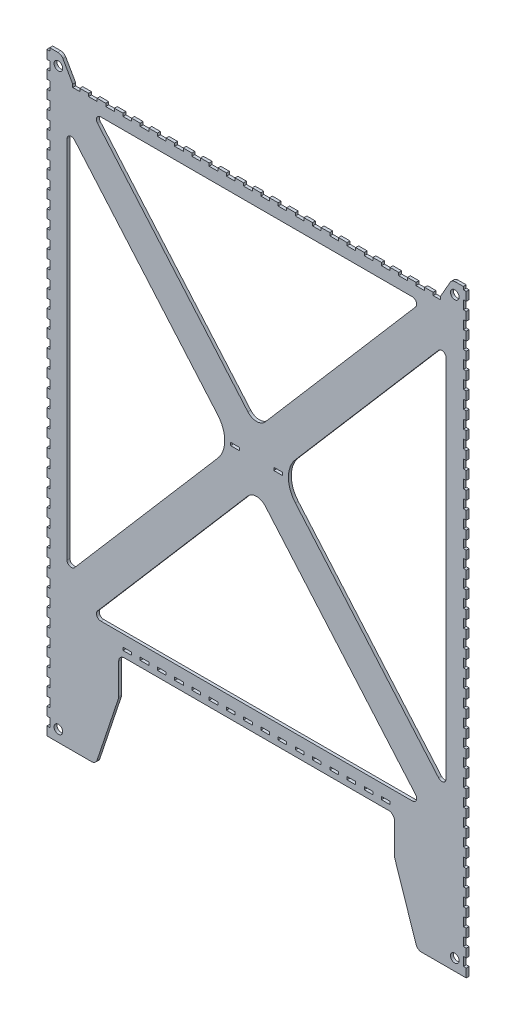
SolidWorks part; units mm, degrees
material "ABS"
ref_plane "Front Plane" through (0, 0, 0) normal (0, 0, 1) x (1, 0, 0)
ref_plane "Top Plane" through (0, 0, 0) normal (0, 1, 0) x (1, 0, 0)
ref_plane "Right Plane" through (0, 0, 0) normal (1, 0, 0) x (0, 0, -1)
sketch "Sketch1" plane through (0, 0, 0) normal (0, 0, 1) x (1, 0, 0)
  line L1 (-114.3, -127) -> (114.3, -127)
  line L2 (-114.3, -127) -> (-114.3, 127)
  line L3 (-114.3, 127) -> (114.3, 127)
  line L4 (114.3, -127) -> (114.3, 127)
  line L5 (-114.3, -127) -> (114.3, 127) construction
  line L6 (-114.3, 127) -> (114.3, -127) construction
  point P0 (0, 0)
  dimension "D1" = 254
  dimension "D2" = 228.6
extrude "Boss-Extrude1" add sketch "Sketch1" along normal mid plane 1.5875
sketch "Sketch2" plane through (0, 0, 0.7937) normal (0, 0, 1) x (1, 0, 0)
  line L0 (-114.3, -127) -> (-114.3, -190.5)
  line L1 (-114.3, -190.5) -> (-88.9, -190.5)
  line L2 (-88.9, -190.5) -> (-76.2, -152.4)
  line L3 (-76.2, -152.4) -> (-76.2, -127)
  line L4 (-114.3, -127) -> (114.3, -127) construction
  line L5 (-76.2, -127) -> (-114.3, -127)
  line L6 (114.3, -127) -> (114.3, -190.5)
  line L7 (114.3, -190.5) -> (88.9, -190.5)
  line L8 (88.9, -190.5) -> (76.2, -152.4)
  line L9 (76.2, -152.4) -> (76.2, -127)
  line L10 (114.3, -127) -> (76.2, -127)
  line L11 (-114.3, 127) -> (-114.3, 139.7)
  line L12 (-114.3, 139.7) -> (-107.95, 139.7)
  line L13 (-107.95, 139.7) -> (-101.6, 128.5875)
  line L14 (114.3, 127) -> (-114.3, 127) construction
  line L15 (-101.6, 127) -> (-114.3, 127)
  line L16 (114.3, 127) -> (114.3, 139.7)
  line L17 (114.3, 139.7) -> (107.95, 139.7)
  line L18 (-101.6, 128.5875) -> (-101.6, 127)
  line L19 (101.6, 127) -> (114.3, 127)
  line L20 (107.95, 139.7) -> (101.6, 128.5875)
  line L21 (101.6, 128.5875) -> (101.6, 127)
  dimension "D1" = 63.5
  dimension "D2" = 25.4
  dimension "D3" = 25.4
  dimension "D4" = 38.1
  dimension "D5" = 12.7
  dimension "D6" = 6.35
  dimension "D7" = 12.7
  dimension "D8" = 1.5875
extrude "Boss-Extrude2" add sketch "Sketch2" against normal up to surface (1.5875 mm away) up to face at (0, 0, -0.7937)
sketch "Sketch4" plane through (0, 0, 0.7937) normal (0, 0, 1) x (1, 0, 0)
  line L0 (-114.3, 139.7) -> (-114.3, -190.5) construction
  line L1 (-114.3, 138.1125) -> (-115.8875, 138.1125)
  line L2 (-114.3, 138.1125) -> (-114.3, 133.35)
  line L3 (-114.3, 133.35) -> (-115.8875, 133.35)
  line L4 (-115.8875, 138.1125) -> (-115.8875, 133.35)
  line L5 (-107.95, 139.7) -> (-114.3, 139.7) construction
  dimension "D1" = 4.7625
  dimension "D2" = 1.5875
  dimension "D3" = 1.5875
extrude "Boss-Extrude3" add sketch "Sketch4" against normal up to surface (1.5875 mm away) up to face at (1.5875, -16.5199, -0.7937)
pattern_linear "LPattern1" count 35 spacing 9.525 along (0, -1, 0) of "Boss-Extrude3"
mirror "Mirror1" about plane through (0, 0, 0) normal (1, 0, 0) of "LPattern1"
sketch "Sketch5" plane through (0, 0, 0.7937) normal (0, 0, 1) x (1, 0, 0)
  line L0 (101.6, 127) -> (-101.6, 127) construction
  line L1 (-97.6312, 127) -> (-92.8688, 127)
  line L2 (-97.6312, 127) -> (-97.6313, 128.5875)
  line L3 (-97.6313, 128.5875) -> (-92.8688, 128.5875)
  line L4 (-92.8688, 127) -> (-92.8688, 128.5875)
  line L6 (-101.6, 127) -> (-101.6, 128.5875) construction
  dimension "D1" = 4.7625
  dimension "D2" = 1.5875
  dimension "D3" = 3.9688
extrude "Boss-Extrude4" add sketch "Sketch5" against normal up to surface (1.5875 mm away) up to face at (0.087, -23.4129, -0.7937)
pattern_linear "LPattern2" count 21 spacing 9.525 along (1, 0, 0) of "Boss-Extrude4"
mirror "Mirror2" about plane through (0, 0, 0) normal (0, 1, 0) of "LPattern2"
sketch "Sketch3" plane through (0, 0, 0.7937) normal (0, 0, 1) x (1, 0, 0)
  line L0 (-91.3046, 120.65) -> (91.3046, 120.65)
  line L1 (91.3046, 120.65) -> (0, 14.561)
  line L2 (0, 14.561) -> (-91.3046, 120.65)
  line L3 (-104.775, 107.1796) -> (-104.775, -107.1796)
  line L4 (-104.775, -107.1796) -> (-12.5318, 0)
  line L5 (-12.5318, 0) -> (-104.775, 107.1796)
  line L6 (104.775, 107.1796) -> (12.5318, 0)
  line L7 (12.5318, 0) -> (104.775, -107.1796)
  line L8 (104.775, -107.1796) -> (104.775, 107.1796)
  line L9 (91.3046, -120.65) -> (-91.3046, -120.65)
  line L10 (-91.3046, -120.65) -> (0, -14.561)
  line L11 (0, -14.561) -> (91.3046, -120.65)
  line L12 (-104.775, 107.1796) -> (-91.3046, 107.1796) construction
  line L13 (104.775, -120.65) -> (-104.775, -120.65) construction
  line L14 (104.775, -120.65) -> (104.775, 120.65) construction
  line L15 (104.775, 120.65) -> (-104.775, 120.65) construction
  line L16 (-104.775, -120.65) -> (-104.775, 120.65) construction
  line L17 (104.775, -120.65) -> (-104.775, 120.65) construction
  line L18 (104.775, 120.65) -> (-104.775, -120.65) construction
  line L19 (-91.3046, 107.1796) -> (-91.3046, 120.65) construction
  line L20 (91.3046, 120.65) -> (91.3046, 107.1796) construction
  line L21 (91.3046, 107.1796) -> (104.775, 107.1796) construction
  line L22 (-104.775, 107.1796) -> (-91.3046, 120.65) construction
  line L23 (91.3046, 120.65) -> (104.775, 107.1796) construction
  line L24 (-104.775, -107.1796) -> (-91.3046, -107.1796) construction
  line L25 (-91.3046, -107.1796) -> (-91.3046, -120.65) construction
  line L26 (91.3046, -120.65) -> (91.3046, -107.1796) construction
  line L27 (91.3046, -107.1796) -> (104.775, -107.1796) construction
  point P9 (0, 0)
  dimension "D1" = 209.55
  dimension "D2" = 241.3
  dimension "D3" = 19.05
extrude "Cut-Extrude1" cut sketch "Sketch3" against normal through all
fillet "Fillet1" radius 15.875 2 edges at (12.5318, 0, 0) (-12.5318, 0, 0)
fillet "Fillet2" radius 2.3813 8 edges at (104.775, -107.1796, 0) (91.3046, -120.65, 0) (91.3046, 120.65, 0) (104.775, 107.1796, 0) (-91.3046, 120.65, 0) (-104.775, 107.1796, 0) (-104.775, -107.1796, 0) (-91.3046, -120.65, 0)
fillet "Fillet3" radius 6.35 2 edges at (0, -14.561, 0) (0, 14.561, 0)
sketch "Sketch6" plane through (0, 0, 0.7937) normal (0, 0, 1) x (1, 0, 0)
  line L0 (-9.525, 0.7938) -> (9.525, -0.7937) construction
  line L1 (-14.2875, -0.7937) -> (-9.525, -0.7937)
  line L2 (-14.2875, -0.7937) -> (-14.2875, 0.7938)
  line L3 (-14.2875, 0.7938) -> (-9.525, 0.7938)
  line L4 (-9.525, -0.7937) -> (-9.525, 0.7938)
  line L5 (-14.2875, -0.7937) -> (-9.525, 0.7938) construction
  line L6 (-14.2875, 0.7938) -> (-9.525, -0.7937) construction
  line L7 (9.525, -0.7937) -> (14.2875, -0.7937)
  line L8 (9.525, -0.7937) -> (9.525, 0.7938)
  line L9 (9.525, 0.7938) -> (14.2875, 0.7938)
  line L10 (14.2875, -0.7937) -> (14.2875, 0.7938)
  line L11 (9.525, -0.7937) -> (14.2875, 0.7938) construction
  line L12 (9.525, 0.7938) -> (14.2875, -0.7937) construction
  point P0 (-11.9062, 0)
  point P5 (11.9063, 0)
  dimension "D1" = 4.7625
  dimension "D2" = 19.05
  dimension "D3" = 1.5875
extrude "Cut-Extrude2" cut sketch "Sketch6" against normal through all
sketch "Sketch7" plane through (0, 0, -0.7937) normal (0, 0, -1) x (-1, 0, 0)
  line L0 (-76.2, -128.5875) -> (-73.8188, -128.5875) construction
  line L1 (-76.2, -128.5875) -> (76.2, -128.5875)
  line L2 (-76.2, -128.5875) -> (-76.2, -131.7625)
  line L3 (-76.2, -131.7625) -> (76.2, -131.7625)
  line L4 (76.2, -128.5875) -> (76.2, -131.7625)
  line L5 (76.2, -152.4) -> (76.2, -128.5875) construction
  dimension "D1" = 3.175
extrude "Boss-Extrude5" add sketch "Sketch7" against normal up to surface (1.5875 mm away) up to face at (11.9062, 0, 0.7937)
sketch "Sketch8" plane through (0, 0, 0.7937) normal (0, 0, 1) x (1, 0, 0)
  line L1 (-109.5375, -184.15) -> (109.5375, -184.15) construction
  line L2 (-109.5375, -184.15) -> (-109.5375, 133.35) construction
  line L3 (-109.5375, 133.35) -> (109.5375, 133.35) construction
  line L4 (109.5375, -184.15) -> (109.5375, 133.35) construction
  line L5 (-109.5375, -184.15) -> (109.5375, 133.35) construction
  line L6 (-109.5375, 133.35) -> (109.5375, -184.15) construction
  line L8 (-107.95, 139.7) -> (-114.3, 139.7) construction
  line L9 (-114.3, 133.35) -> (-114.3, 128.5875) construction
  line L10 (-115.8875, -190.5) -> (-88.9, -190.5) construction
  circle A0 centre (-109.5375, 133.35) radius 2.3813
  circle A1 centre (-109.5375, -184.15) radius 2.3813
  circle A2 centre (109.5375, 133.35) radius 2.3813
  circle A3 centre (109.5375, -184.15) radius 2.3813
  point P0 (0, -25.4)
  point P15 (-102.3938, -190.5)
  dimension "D2" = 4.7625
  dimension "D1" = 6.35
  dimension "D3" = 4.7625
  dimension "D4" = 6.35
extrude "Cut-Extrude3" cut sketch "Sketch8" against normal through all
fillet "Fillet4" radius 3.175 6 edges at (88.9, -190.5, 0) (76.2, -152.4, 0) (76.2, -131.7625, 0) (-76.2, -131.7625, 0) (-76.2, -152.4, 0) (-88.9, -190.5, 0)
fillet "Fillet5" radius 3.175 2 edges at (107.95, 139.7, 0) (-107.95, 139.7, 0)
